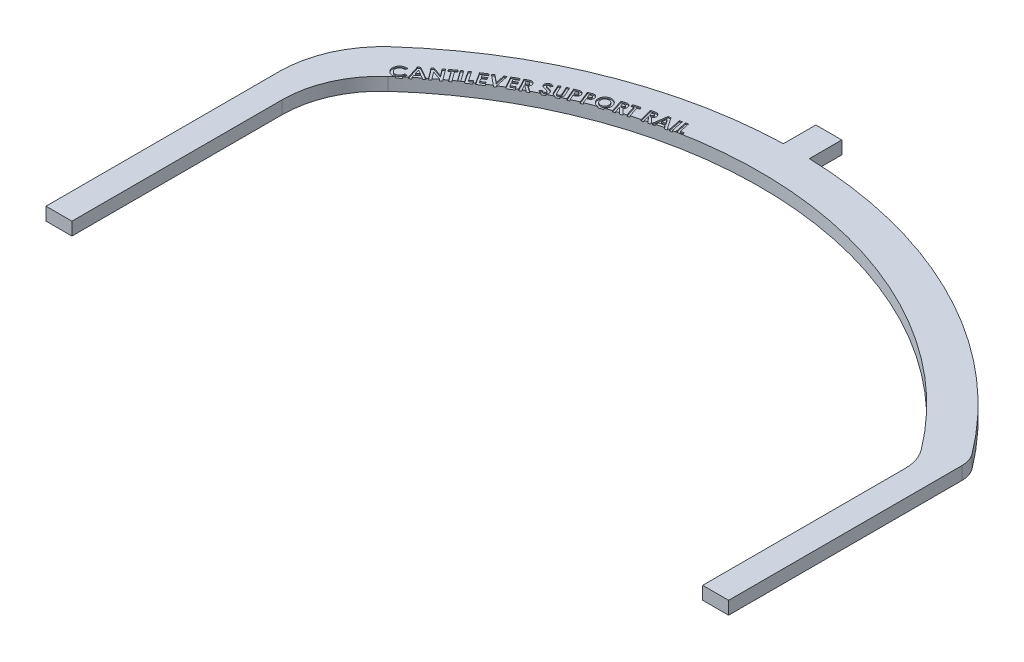
SolidWorks part; units mm, degrees
ref_plane "Front Plane" through (0, 0, 0) normal (0, 0, 1) x (1, 0, 0)
ref_plane "Top Plane" through (0, 0, 0) normal (0, 1, 0) x (1, 0, 0)
ref_plane "Right Plane" through (0, 0, 0) normal (1, 0, 0) x (0, 0, -1)
sketch "Sketch1" plane through (0, 0, 0) normal (0, 1, 0) x (1, 0, 0)
  line L2 (1832.2756, 6.35) -> (1832.2756, 281.3391) construction
  line L3 (1819.5756, 435.4221) -> (1819.5756, 467.1721)
  line L4 (1819.5756, 467.1721) -> (1844.9756, 467.1721)
  line L5 (1844.9756, 467.1721) -> (1844.9756, 435.4221)
  line L6 (1545.0446, 325.3523) -> (1568.8389, 298.9261) construction
  line L7 (1511.4283, 21.2488) -> (1536.8283, 21.2488)
  line L8 (1511.4283, 21.2488) -> (1511.4283, 249.8488)
  line L10 (1536.8283, 21.2488) -> (1536.8283, 227.0291)
  line L12 (2154.6621, 219.4838) -> (2154.6621, 21.2488)
  line L13 (2154.6621, 21.2488) -> (2180.0621, 21.2488)
  line L14 (2180.0621, 249.8488) -> (2180.0621, 21.2488)
  line L15 (2175.0979, 264.6851) -> (2146.6984, 243.2846) construction
  arc A0 (1545.0446, 325.3523) -> (1819.5756, 435.4221) centre (1832.2756, 6.35) cw
  arc A1 (1568.8389, 298.9261) -> (2146.6984, 243.2846) centre (1832.2756, 6.35) cw
  arc A2 (1844.9756, 435.4221) -> (2175.0979, 264.6851) centre (1832.2756, 6.35) cw
  arc A3 (1545.0446, 325.3523) -> (1511.4283, 249.8488) centre (1613.0283, 249.8488) ccw
  arc A4 (1568.8389, 298.9261) -> (1536.8283, 227.0291) centre (1633.5753, 227.0291) ccw
  arc A5 (2146.6984, 243.2846) -> (2154.6621, 219.4838) centre (2115.1137, 219.4838) cw
  arc A6 (2175.0979, 264.6851) -> (2180.0621, 249.8488) centre (2155.4095, 249.8488) cw
  point P0 (1019.9264, 43.1835)
  dimension "D1" = 393.7
  dimension "D4" = 101.6
  dimension "D2" = 35.56
  dimension "D3" = 228.6
  dimension "D5" = 25.4
  dimension "D6" = 31.75
  dimension "D7" = 42
  dimension "D8" = 53
  dimension "D9" = 12.7
  dimension "D10" = 6.35
  dimension "D11" = 25.4
  dimension "D12" = 25.4
extrude "Boss-Extrude1" add sketch "Sketch1" along normal blind 12.7
sketch "Sketch2" plane through (0, 12.7, 0) normal (0, 1, 0) x (1, 0, 0)
  text T0 "CANTILEVER SUPPORT RAIL" font "Century Gothic" height 12.7
extrude "Cut-Extrude1" cut sketch "Sketch2" against normal blind 1.27
